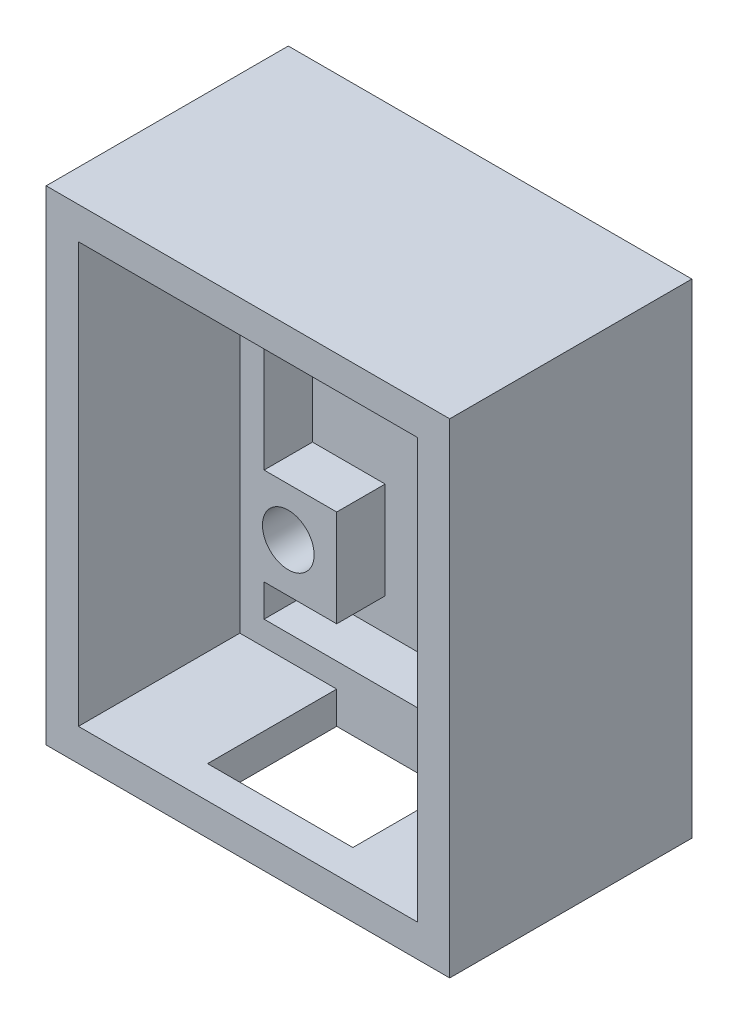
SolidWorks part; units mm, degrees
ref_plane "正面" through (0, 0, 0) normal (0, 0, 1) x (1, 0, 0)
ref_plane "平面" through (0, 0, 0) normal (0, 1, 0) x (1, 0, 0)
ref_plane "右側面" through (0, 0, 0) normal (1, 0, 0) x (0, 0, -1)
sketch "ｽｹｯﾁ1" plane through (0, 0, 0) normal (0, 0, 1) x (1, 0, 0)
  line L1 (-83.9031, 40.6786) -> (-58.9031, 40.6786)
  line L2 (-83.9031, 40.6786) -> (-83.9031, 10.6786)
  line L3 (-83.9031, 10.6786) -> (-58.9031, 10.6786)
  line L4 (-58.9031, 40.6786) -> (-58.9031, 10.6786)
  dimension "D1" = 30
  dimension "D2" = 25
extrude "ﾎﾞｽ - 押し出し1" add sketch "ｽｹｯﾁ1" along normal blind 15
sketch "ｽｹｯﾁ2" plane through (0, 0, 15) normal (0, 0, 1) x (1, 0, 0)
  line L0 (-58.9031, 40.6786) -> (-83.9031, 40.6786) construction
  line L1 (-81.9031, 38.6786) -> (-60.9031, 38.6786)
  line L2 (-81.9031, 38.6786) -> (-81.9031, 12.6786)
  line L3 (-81.9031, 12.6786) -> (-60.9031, 12.6786)
  line L4 (-60.9031, 38.6786) -> (-60.9031, 12.6786)
  line L5 (-83.9031, 10.6786) -> (-58.9031, 10.6786) construction
  line L6 (-58.9031, 10.6786) -> (-58.9031, 40.6786) construction
  line L7 (-83.9031, 40.6786) -> (-83.9031, 10.6786) construction
  dimension "D1" = 26
  dimension "D2" = 21
  dimension "D3" = 2
  dimension "D4" = 2
  dimension "D5" = 2
  dimension "D6" = 2
extrude "ｶｯﾄ - 押し出し1" cut sketch "ｽｹｯﾁ2" against normal blind 13
sketch "ｽｹｯﾁ3" plane through (0, 0, 2) normal (0, 0, 1) x (1, 0, 0)
  line L1 (-60.9031, 38.6786) -> (-81.9031, 38.6786)
  line L2 (-60.9031, 38.6786) -> (-60.9031, 12.6786)
  line L3 (-60.9031, 12.6786) -> (-81.9031, 12.6786)
  line L4 (-81.9031, 38.6786) -> (-81.9031, 12.6786)
  line L5 (-80.4031, 37.1786) -> (-62.4031, 37.1786)
  line L6 (-80.4031, 37.1786) -> (-80.4031, 14.1786)
  line L7 (-80.4031, 14.1786) -> (-62.4031, 14.1786)
  line L8 (-62.4031, 37.1786) -> (-62.4031, 14.1786)
  dimension "D1" = 1.5
  dimension "D2" = 1.5
  dimension "D3" = 1.5
  dimension "D4" = 1.5
extrude "ﾎﾞｽ - 押し出し2" add sketch "ｽｹｯﾁ3" along normal blind 3
sketch "ｽｹｯﾁ5" plane through (0, 0, 2) normal (0, 0, 1) x (1, 0, 0)
  line L0 (-62.4031, 14.1786) -> (-62.4031, 37.1786) construction
  line L1 (-62.4031, 22.1786) -> (-66.9031, 22.1786)
  line L2 (-62.4031, 22.1786) -> (-62.4031, 16.1786)
  line L3 (-62.4031, 16.1786) -> (-66.9031, 16.1786)
  line L4 (-66.9031, 22.1786) -> (-66.9031, 16.1786)
  line L6 (-81.9031, 12.6786) -> (-60.9031, 12.6786) construction
  line L7 (-80.4031, 37.1786) -> (-80.4031, 14.1786) construction
  line L8 (-80.4031, 22.1786) -> (-75.9031, 22.1786)
  line L9 (-80.4031, 22.1786) -> (-80.4031, 16.1786)
  line L10 (-80.4031, 16.1786) -> (-75.9031, 16.1786)
  line L11 (-75.9031, 22.1786) -> (-75.9031, 16.1786)
  point P10 (-66.9031, 19.1786)
  point P15 (-75.9031, 19.1786)
  dimension "D1" = 4.5
  dimension "D2" = 6
  dimension "D3" = 6.5
  dimension "D4" = 6.5
extrude "ﾎﾞｽ - 押し出し3" add sketch "ｽｹｯﾁ5" along normal blind 3
sketch "ｽｹｯﾁ6" plane through (0, 0, 5) normal (0, 0, 1) x (1, 0, 0)
  line L0 (-66.9031, 22.1786) -> (-66.9031, 16.1786) construction
  line L1 (-66.9031, 16.1786) -> (-62.4031, 16.1786) construction
  line L2 (-75.9031, 16.1786) -> (-75.9031, 22.1786) construction
  line L3 (-80.4031, 16.1786) -> (-75.9031, 16.1786) construction
  circle A0 centre (-63.9031, 19.1786) radius 1.6
  circle A1 centre (-78.9031, 19.1786) radius 1.6
  point P4 (0, 0)
  dimension "D1" = 3.2
  dimension "D4" = 3
  dimension "D5" = 3
  dimension "D2" = 3
  dimension "D3" = 3
extrude "ｶｯﾄ - 押し出し2" cut sketch "ｽｹｯﾁ6" against normal through all
sketch "ｽｹｯﾁ7" plane through (0, 12.6786, 0) normal (0, 1, 0) x (1, 0, 0)
  line L0 (-81.9031, -5) -> (-60.9031, -5) construction
  line L1 (-66.9031, -5) -> (-75.9031, -5)
  line L2 (-66.9031, -5) -> (-66.9031, -13)
  line L3 (-66.9031, -13) -> (-75.9031, -13)
  line L4 (-75.9031, -5) -> (-75.9031, -13)
  line L5 (-81.9031, -15) -> (-60.9031, -15) construction
  line L6 (-60.9031, -5) -> (-60.9031, -15) construction
  line L7 (-81.9031, -5) -> (-81.9031, -15) construction
  dimension "D1" = 2
  dimension "D2" = 6
  dimension "D3" = 6
extrude "ｶｯﾄ - 押し出し3" cut sketch "ｽｹｯﾁ7" against normal through all
